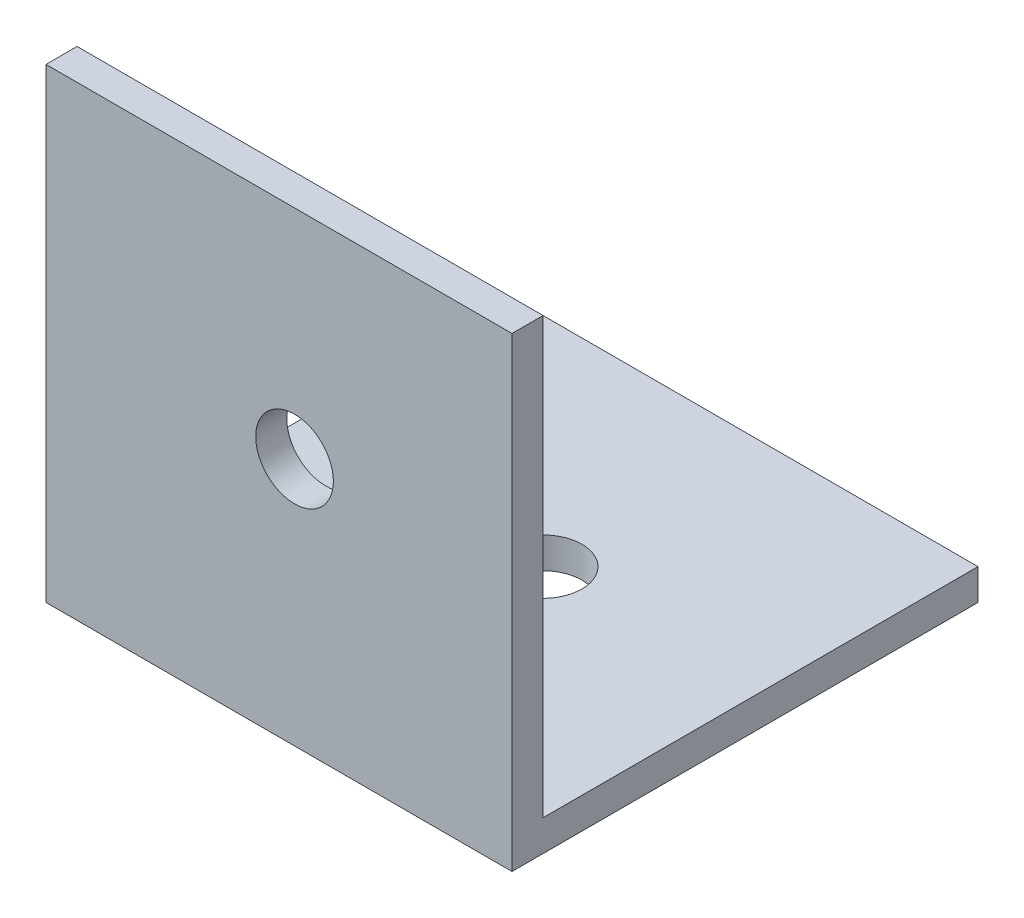
SolidWorks part; units mm, degrees
ref_plane "正面" through (0, 0, 0) normal (0, 0, 1) x (1, 0, 0)
ref_plane "平面" through (0, 0, 0) normal (0, 1, 0) x (1, 0, 0)
ref_plane "右側面" through (0, 0, 0) normal (1, 0, 0) x (0, 0, -1)
sketch "ｽｹｯﾁ1" plane through (0, 0, 0) normal (0, 0, 1) x (1, 0, 0)
  line L1 (0, 0) -> (15, 0)
  line L2 (0, 0) -> (0, 15)
  line L3 (0, 15) -> (15, 15)
  line L4 (15, 0) -> (15, 15)
  dimension "D1" = 15
  dimension "D2" = 15
extrude "ﾎﾞｽ - 押し出し1" add sketch "ｽｹｯﾁ1" along normal blind 1
sketch "ｽｹｯﾁ2" plane through (0, 0, 1) normal (0, 0, 1) x (1, 0, 0)
  line L0 (15, 0) -> (15, 15) construction
  line L1 (0, 0) -> (15, 0)
  line L2 (0, 0) -> (0, 1)
  line L3 (0, 1) -> (15, 1)
  line L4 (15, 0) -> (15, 1)
  dimension "D1" = 1
extrude "ﾎﾞｽ - 押し出し2" add sketch "ｽｹｯﾁ2" against normal blind 15
hole_wizard "M3x0.5 ねじ穴1" positions "ｽｹｯﾁ3" profile "ｽｹｯﾁ4" tap size "M3x0.5" standard "JIS" end condition through all
sketch "ｽｹｯﾁ3" plane through (0, 0, 1) normal (0, 0, 1) x (1, 0, 0)
  line L0 (15, 15) -> (0, 15) construction
  line L1 (0, 15) -> (0, 0) construction
  point P0 (8, 8)
  dimension "D1" = 7
  dimension "D2" = 8
sketch "ｽｹｯﾁ4" plane through (8, 8, 1) normal (1, 0, 0) x (0, -1, 0)
  line L0 (0, 0) -> (0, 15)
  line L1 (0, 15) -> (1.25, 15)
  line L2 (1.25, 15) -> (1.25, 0)
  line L5 (1.25, 0) -> (0, 0)
  line L11 (0, -6.35) -> (0, 107.95) construction
  dimension "次ｻｰﾌｪｽまでのねじ下穴ﾄﾞﾘﾙ直径" = 2.5
  dimension "次ｻｰﾌｪｽまでのねじ下穴ﾄﾞﾘﾙの深さ" = 15
cosmetic thread "穴のねじ山1" parameters "D2"=3
hole_wizard "M3x0.5 ねじ穴2" positions "ｽｹｯﾁ5" profile "ｽｹｯﾁ6" tap size "M3x0.5" standard "JIS" end condition through all
sketch "ｽｹｯﾁ5" plane through (0, 0, 0) normal (0, -1, 0) x (-1, 0, 0)
  line L0 (0, -1) -> (0, 14) construction
  line L1 (0, 14) -> (-15, 14) construction
  point P0 (-8, 7)
  dimension "D1" = 8
  dimension "D2" = 7
sketch "ｽｹｯﾁ6" plane through (8, 0, -7) normal (1, 0, 0) x (0, 0, -1)
  line L0 (0, 0) -> (0, 15)
  line L1 (0, 15) -> (1.25, 15)
  line L2 (1.25, 15) -> (1.25, 0)
  line L5 (1.25, 0) -> (0, 0)
  line L11 (0, -6.35) -> (0, 107.95) construction
  dimension "次ｻｰﾌｪｽまでのねじ下穴ﾄﾞﾘﾙ直径" = 2.5
  dimension "次ｻｰﾌｪｽまでのねじ下穴ﾄﾞﾘﾙの深さ" = 15
cosmetic thread "穴のねじ山2" parameters "D2"=3
